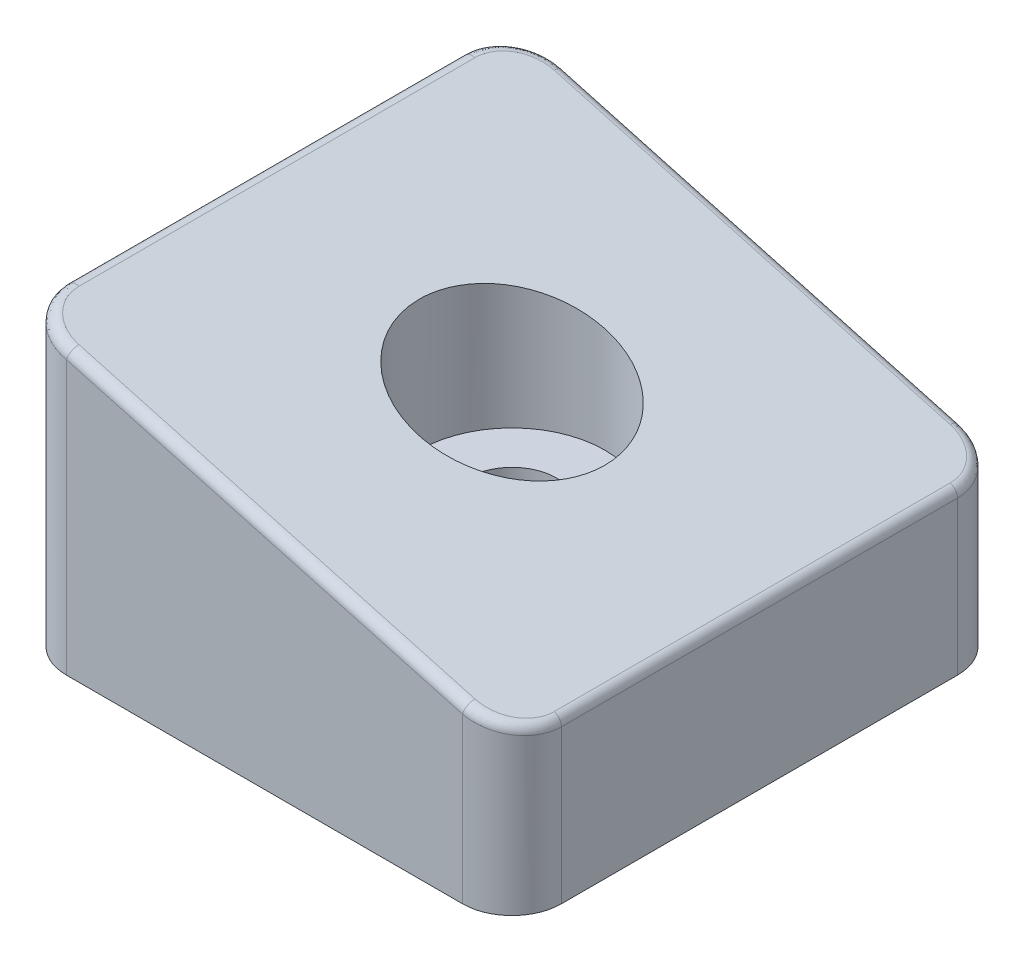
SolidWorks part; units mm, degrees
ref_plane "Front Plane" through (0, 0, 0) normal (0, 0, 1) x (1, 0, 0)
ref_plane "Top Plane" through (0, 0, 0) normal (0, 1, 0) x (1, 0, 0)
ref_plane "Right Plane" through (0, 0, 0) normal (1, 0, 0) x (0, 0, -1)
sketch "Sketch1" plane through (0, 0, 0) normal (0, 0, 1) x (1, 0, 0)
  line L0 (0, 0) -> (101.6, 0) construction
  line L1 (0, 0) -> (0, 27.94) construction
  line L2 (101.6, 0) -> (0, 27.94) construction
  line L3 (0, 0) -> (25.4, 0) construction
  line L4 (0, 0) -> (0, 12.7) construction
  line L5 (0, 12.7) -> (25.4, 12.7) construction
  line L6 (25.4, 0) -> (25.4, 12.7) construction
  line L7 (0, 27.94) -> (0, 12.7)
  line L8 (0, 12.7) -> (25.4, 12.7)
  line L9 (25.4, 12.7) -> (25.4, 20.955)
  line L10 (25.4, 20.955) -> (0, 27.94)
  dimension "D1" = 101.6
  dimension "D2" = 27.94
  dimension "D3" = 12.7
  dimension "D4" = 25.4
extrude "Boss-Extrude1" add sketch "Sketch1" against normal blind 25.4
ref_plane "Plane1" through (0, 38.1, 0) normal (0, -1, 0) x (-1, 0, 0)
sketch "Sketch2" plane through (0, 38.1, 0) normal (0, -1, 0) x (-1, 0, 0)
  line L0 (-25.4, 25.4) -> (0, 0) construction
  circle A0 centre (-12.7, 12.7) radius 4.7625
  circle A1 centre (-12.7, 12.7) radius 2.286
  point P7 (-12.7, 12.7)
  point P8 (0, 0)
  dimension "D1" = 9.525
  dimension "D2" = 4.572
extrude "Cut-Extrude1" cut sketch "Sketch2" along normal through all contours A1 L0 | L0 A1 region at (12.014, 38.1, -13.386) region at (13.386, 38.1, -12.014)
extrude "Cut-Extrude2" cut sketch "Sketch2<3>" along normal offset from surface (19.05 mm away) 6.35 contours L0 A0 A1 | A0 L0 A1 region at (11.0482, 38.1, -14.3518) region at (14.3518, 38.1, -11.0482) up to face at (12.7, 12.7, -14.986)
sketch "Sketch2<3>" plane through (0, 38.1, 0) normal (0, -1, 0) x (-1, 0, 0) same geometry as "Sketch2"
fillet "Fillet1" radius 2.54 4 edges at (0, 20.32, 0) (0, 20.32, -25.4) (25.4, 16.8275, -25.4) (25.4, 16.8275, 0)
fillet "Fillet2" radius 0.508 8 edges at (24.6561, 21.1596, -0.7439) (25.4, 20.955, -12.7) (24.6561, 21.1596, -24.6561) (12.7, 24.4475, -25.4) (0.7439, 27.7354, -24.6561) (0, 27.94, -12.7) (0.7439, 27.7354, -0.7439) (12.7, 24.4475, 0)
